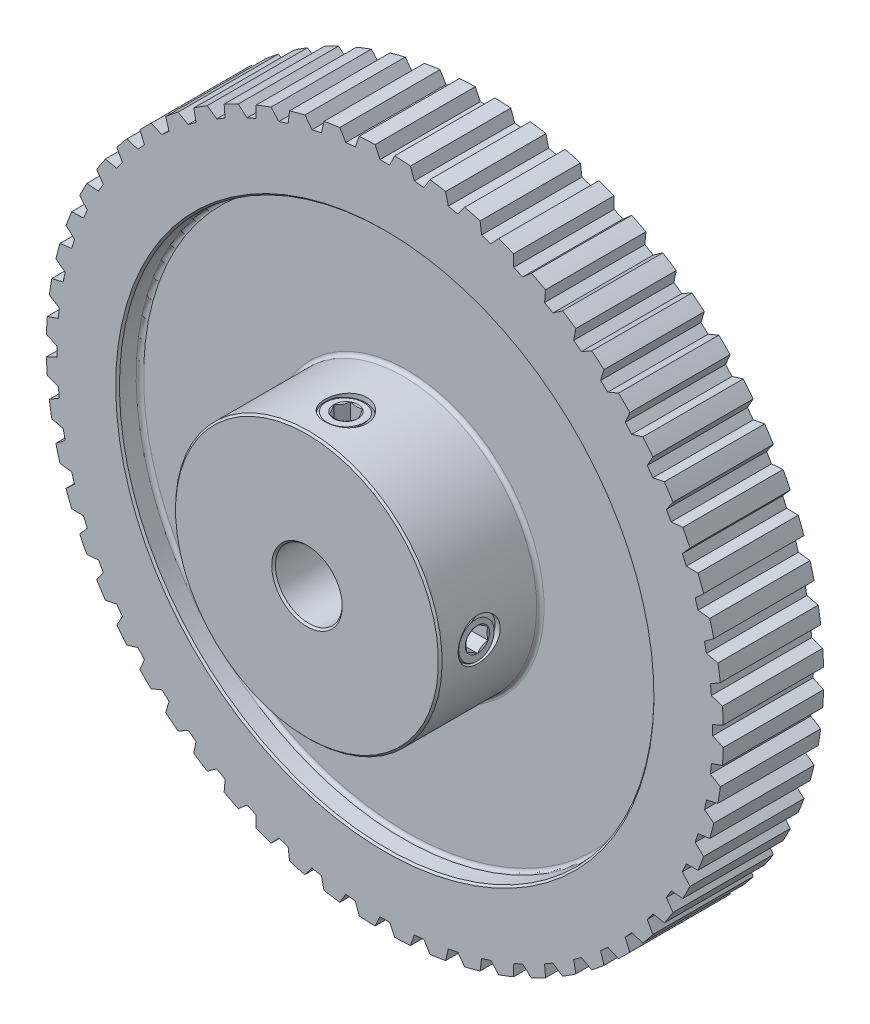
SolidWorks part; units mm, degrees
ref_plane "Front Plane" through (0, 0, 0) normal (0, 0, 1) x (1, 0, 0)
ref_plane "Top Plane" through (0, 0, 0) normal (0, 1, 0) x (1, 0, 0)
ref_plane "Right Plane" through (0, 0, 0) normal (1, 0, 0) x (0, 0, -1)
sketch "Sketch1" plane through (0, 0, 0) normal (0, 0, 1) x (1, 0, 0)
  line L0 (-1.2827, 48.006) -> (-0.6905, 46.736)
  line L1 (-0.6905, 46.736) -> (0.6905, 46.736)
  line L2 (0.6905, 46.736) -> (1.2827, 48.006)
  line L3 (-1.2827, 48.006) -> (1.2827, 48.006)
  line L4 (0, 0) -> (0, 46.736) construction
  line L5 (0, 46.736) -> (0, 49.022) construction
  circle A0 centre (0, 0) radius 48.514 construction
  circle A1 centre (0, 0) radius 48.26 construction
  circle A2 centre (0, 0) radius 48.0231 construction
  arc A3 (0, 48.26) -> (5.0706, 47.9929) centre (0, 0) cw
  point P6 (0, 48.006)
  point P11 (0, 48.514)
  point P13 (0, 48.26)
  point P14 (0, 48.0231)
  point P18 (19.5328, 43.8713)
  point P19 (24.0116, 41.5893)
  point P20 (28.2273, 38.8515)
  point P21 (5.0198, 47.7601)
  point P22 (9.9846, 46.9737)
  point P23 (14.84, 45.6727)
  point P24 (0, 0)
  point P25 (32.1337, 35.6881)
  point P26 (35.6881, 32.1337)
  point P27 (38.8515, 28.2273)
  point P28 (41.5893, 24.0116)
  point P29 (43.8713, 19.5328)
  point P30 (45.6727, 14.84)
  point P31 (46.9737, 9.9846)
  point P32 (47.7601, 5.0198)
  point P33 (48.0231, 0)
  point P34 (47.7601, -5.0198)
  point P35 (46.9737, -9.9846)
  point P36 (45.6727, -14.84)
  point P37 (43.8713, -19.5328)
  point P38 (41.5893, -24.0116)
  point P39 (38.8515, -28.2273)
  point P40 (35.6881, -32.1337)
  point P41 (32.1337, -35.6881)
  point P42 (28.2273, -38.8515)
  point P43 (24.0116, -41.5893)
  point P44 (19.5328, -43.8713)
  point P45 (14.84, -45.6727)
  point P46 (9.9846, -46.9737)
  point P47 (5.0198, -47.7601)
  point P48 (0, -48.0231)
  point P49 (-5.0198, -47.7601)
  point P50 (-9.9846, -46.9737)
  point P51 (-14.84, -45.6727)
  point P52 (-19.5328, -43.8713)
  point P53 (-24.0116, -41.5893)
  point P54 (-28.2273, -38.8515)
  point P55 (-32.1337, -35.6881)
  point P56 (-35.6881, -32.1337)
  point P57 (-38.8515, -28.2273)
  point P58 (-41.5893, -24.0116)
  point P59 (-43.8713, -19.5328)
  point P60 (-45.6727, -14.84)
  point P61 (-46.9737, -9.9846)
  point P62 (-47.7601, -5.0198)
  point P63 (-48.0231, 0)
  point P64 (-47.7601, 5.0198)
  point P65 (-46.9737, 9.9846)
  point P66 (-45.6727, 14.84)
  point P67 (-43.8713, 19.5328)
  point P68 (-41.5893, 24.0116)
  point P69 (-38.8515, 28.2273)
  point P70 (-35.6881, 32.1337)
  point P71 (-32.1337, 35.6881)
  point P72 (-28.2273, 38.8515)
  point P73 (-24.0116, 41.5893)
  point P74 (-19.5328, 43.8713)
  point P75 (-14.84, 45.6727)
  point P76 (-9.9846, 46.9737)
  point P77 (-5.0198, 47.7601)
  dimension "Pitch Diameter" = 97.028
  dimension "OD" = 96.52
  dimension "Pitch/10" = 0.508
  dimension "Pitch" = 5.08
  dimension "Number of Teeth" = 60
sketch "Sketch2" plane through (0, 0, 0) normal (1, 0, 0) x (0, 0, -1)
  line L0 (-11.1, 0) -> (14.3, 0) construction
  line L1 (-11.1, 19) -> (-11.1, -19) construction
  line L2 (14.3, 4.7625) -> (14.3, -4.7625) construction
  line L3 (-11.1, 19) -> (-8.55, 19) construction
  line L4 (-8.55, 19) -> (-2.55, 19) construction
  line L5 (-2.55, 19) -> (0, 19) construction
  line L6 (0, 48.0231) -> (0, -48.0231) construction
  line L7 (-8.6583, 19.9375) -> (-8.6583, 18.9375) construction
  line L8 (-8.6583, 18.9375) -> (-7.7922, 19.4375) construction
  line L9 (-7.7922, 19.4375) -> (-8.6583, 19.9375) construction
  line L10 (-8.55, 19) -> (-8.55, 19.875) construction
  line L11 (-7.9005, 19.5) -> (-7.9005, 19.375) construction
  line L12 (-7.9005, 19.4375) -> (-7.7922, 19.4375) construction
  line L13 (-8.55, 19.4375) -> (-8.6583, 19.4375) construction
  line L14 (-7.05, 19) -> (-4.05, 19) construction
  line L15 (0, -48.26) -> (2.4, -48.26) construction
  line L16 (2.4, -48.26) -> (11.9, -48.26) construction
  line L17 (11.9, -48.26) -> (14.3, -48.26) construction
  line L18 (0, 48.26) -> (14.3, 48.26) construction
  line L20 (-5.55, 19) -> (-5.55, 4.7625) construction
  point P23 (-5.55, 19)
  point P24 (-7.05, 19)
  point P26 (-4.05, 19)
  point P36 (0, 38.1)
  point P37 (3.175, 38.1)
  point P38 (3.175, 19)
  dimension "Overall Width" = 25.4
  dimension "Outside Width" = 14.3
  dimension "Hub Diameter" = 38
  dimension "For Shaft Diameter" = 9.525
  dimension "Set Screw" = 6
  dimension "Set Screw Pitch" = 1
  dimension "Pitch/8" = 0.125
  dimension "Set Screw Hex" = 3
  dimension "For Maximum Belt Width" = 9.5
  dimension "Cutout Depth" = 3.175
  dimension "Cutout Diameter" = 76.2
sketch "Sketch3" plane through (0, 0, 0) normal (1, 0, 0) x (0, 0, -1)
  line L0 (-11.1, 4.7625) -> (14.3, 4.7625)
  line L1 (-11.1, 4.7625) -> (-11.1, 19)
  line L2 (-11.1, 19) -> (3.175, 19)
  line L3 (0, 38.1) -> (0, 48.26)
  line L4 (0, 38.1) -> (3.175, 38.1)
  line L5 (3.175, 38.1) -> (3.175, 19)
  line L6 (14.3, 38.1) -> (11.125, 38.1)
  line L7 (11.125, 38.1) -> (11.125, 19)
  line L8 (11.125, 19) -> (14.3, 19)
  line L9 (14.3, 48.26) -> (14.3, 38.1)
  line L10 (14.3, 19) -> (14.3, 4.7625)
  line L16 (0, 48.26) -> (14.3, 48.26)
revolve "Revolve1" add sketch "Sketch3" angle 360 about L0
sketch "Sketch4" plane through (0, 0, 0) normal (0, 0, 1) x (1, 0, 0)
  line L0 (-0.6905, 46.736) -> (0.6905, 46.736) construction
  line L1 (0.6905, 46.736) -> (1.2827, 48.006) construction
  line L2 (-1.2827, 48.006) -> (-0.6905, 46.736) construction
  line L3 (-0.6905, 46.736) -> (0.6905, 46.736)
  line L4 (0.6905, 46.736) -> (2.0931, 49.7439)
  line L5 (-2.0931, 49.7439) -> (-0.6905, 46.736)
  circle A0 centre (0, 0) radius 48.26 construction
  circle A1 centre (0, 0) radius 4.7625 construction
  arc A3 (2.0931, 49.7439) -> (-2.0931, 49.7439) centre (0, 0) ccw
  point P7 (-1.3918, 48.2399)
extrude "Cut-Extrude1" cut sketch "Sketch4" against normal through all
pattern_circular "CirPattern1" count 60 over 360 about axis through (0, 0, 0) along (0, 0, 1) of "Cut-Extrude1"
sketch "Sketch5" plane through (0, 0, 0) normal (0, 1, 0) x (0, 0, -1)
  line L3 (-8.55, 0) -> (-2.55, 0) construction
  circle A0 centre (-5.55, 0) radius 3
extrude "Cut-Extrude2" cut sketch "Sketch5" along normal through all
sketch "Sketch6" plane through (0, 0, 0) normal (1, 0, 0) x (0, 0, -1)
  line L0 (-5.55, 0) -> (-5.55, -3) construction
  circle A0 centre (-5.55, 0) radius 3
  point P2 (-2.55, 0)
extrude "Cut-Extrude3" cut sketch "Sketch6" along normal through all
ref_plane "Plane1" through (0, 0, 5.55) normal (0, 0, 1) x (1, 0, 0)
sketch "Sketch7" plane through (0, 0, 5.55) normal (-1, 0, 0) x (0, 0, 1)
  line L1 (-3, 18.42) -> (-3, 5.0925)
  line L2 (-2.67, 18.75) -> (0, 18.75)
  line L3 (0, 18.75) -> (0, 4.7625) construction
  line L4 (-2.67, 4.7625) -> (0, 4.7625)
  line L5 (0, 19) -> (0, 4.7625) construction
  line L6 (5.55, 19) -> (3, 19) construction
  line L23 (0, 4.7625) -> (0, 18.75)
  line L24 (-2.67, 18.75) -> (-3, 18.42)
  line L25 (-3, 5.0925) -> (-2.67, 4.7625)
  dimension "D1" = 45
  dimension "D2" = 0.33
  dimension "D3" = 0.25
revolve "Revolve2" add sketch "Sketch7" angle 360 mid plane about L20
sketch "Sketch8" plane through (0, 18.75, 0) normal (0, 1, 0) x (0, 0, 1)
  line L1 (5.55, 1.7321) -> (4.05, 0.866)
  line L2 (4.05, 0.866) -> (4.05, -0.866)
  line L3 (4.05, -0.866) -> (5.55, -1.7321)
  line L4 (5.55, -1.7321) -> (7.05, -0.866)
  line L5 (7.05, -0.866) -> (7.05, 0.866)
  line L6 (7.05, 0.866) -> (5.55, 1.7321)
  circle A0 centre (5.55, 0) radius 1.5 construction
extrude "Cut-Extrude4" cut sketch "Sketch8" against normal blind 3
sketch "Sketch9" plane through (0, 18.75, 0) normal (0, 1, 0) x (1, 0, 0)
  circle A0 centre (0, -5.55) radius 1.7321
extrude "Cut-Extrude5" cut sketch "Sketch9" against normal through all draft 60
pattern_circular "CirPattern2" count 2 over 90 about axis through (0, 0, 0) along (0, 0, 1) of bodies 111
chamfer "Chamfer1" distance 0.264 angle 45 6 edges at (0, -4.7625, 11.1) (0, -19, 11.1) (0, -4.7625, -14.3) (0, -19, -14.3) (0, -38.1, -14.3) (0, -38.1, 0)
fillet "Fillet1" radius 0.528 4 edges at (0, -38.1, -3.175) (0, -19, -3.175) (0, -38.1, -11.125) (0, -19, -11.125)
delete or keep bodies "Body-Delete/Keep 1" bodies 112
sketch "Sketch10" plane through (0, 18.75, 0) normal (0, 1, 0) x (1, 0, 0)
  circle A0 centre (0, -5.55) radius 3
  circle A1 centre (0, -5.55) radius 3 construction
curve "Helix/Spiral1" pitch 1 height 14.807 turns 14.807
sketch "Sketch11" plane through (0, 0, 0) normal (1, 0, 0) x (0, 0, -1)
  line L0 (-8.6041, 19.6562) -> (-8.6041, 18.7187)
  line L1 (-8.6041, 18.7187) -> (-7.9005, 19.125)
  line L2 (-7.9005, 19.125) -> (-7.9005, 19.25)
  line L3 (-7.9005, 19.25) -> (-8.6041, 19.6562)
  line L4 (-7.9005, 19.5) -> (-7.9005, 19.375) construction
  line L5 (-8.6583, 18.9375) -> (-7.7922, 19.4375) construction
  line L6 (-7.7922, 19.4375) -> (-8.6583, 19.9375) construction
  line L7 (-8.55, 19.4375) -> (-8.6583, 19.4375) construction
  point P12 (-8.6041, 19.4375)
  point P13 (-8.55, 18.75)
sweep "Cut-Sweep1" cut profiles "Sketch11" path "Helix/Spiral1" align with end faces yes
pattern_circular "CirPattern3" count 2 over 90 about axis through (0, 0, 11.1) along (0, 0, -1) of bodies 113
equation "\"Pitch/10@Sketch1\" = \"Pitch@Sketch1\" / 10"
equation "\"Pitch/8@Sketch2\" = \"Set Screw Pitch@Sketch2\" / 8"
equation "\"D1@CirPattern1\"=\"Number of Teeth@Sketch1\""
equation "\"D2@Sketch7\" = \"Set Screw Pitch@Sketch2\" * .33"
equation "\"D1@Cut-Extrude4\" = \"Set Screw@Sketch2\" * .5"
equation "\"DC1@Chamfer\" = \"Set Screw Pitch@Sketch2\" * .33"
equation "\"D4@Helix/Spiral1\"=\"Set Screw Pitch@Sketch2\""
equation "\"D3@Helix/Spiral1\"=(\"Hub Diameter@Sketch2\"-\"For Shaft Diameter@Sketch2\")*.52"
equation "\"D1@Fillet1\"=\"D1@Chamfer1\"*2"
